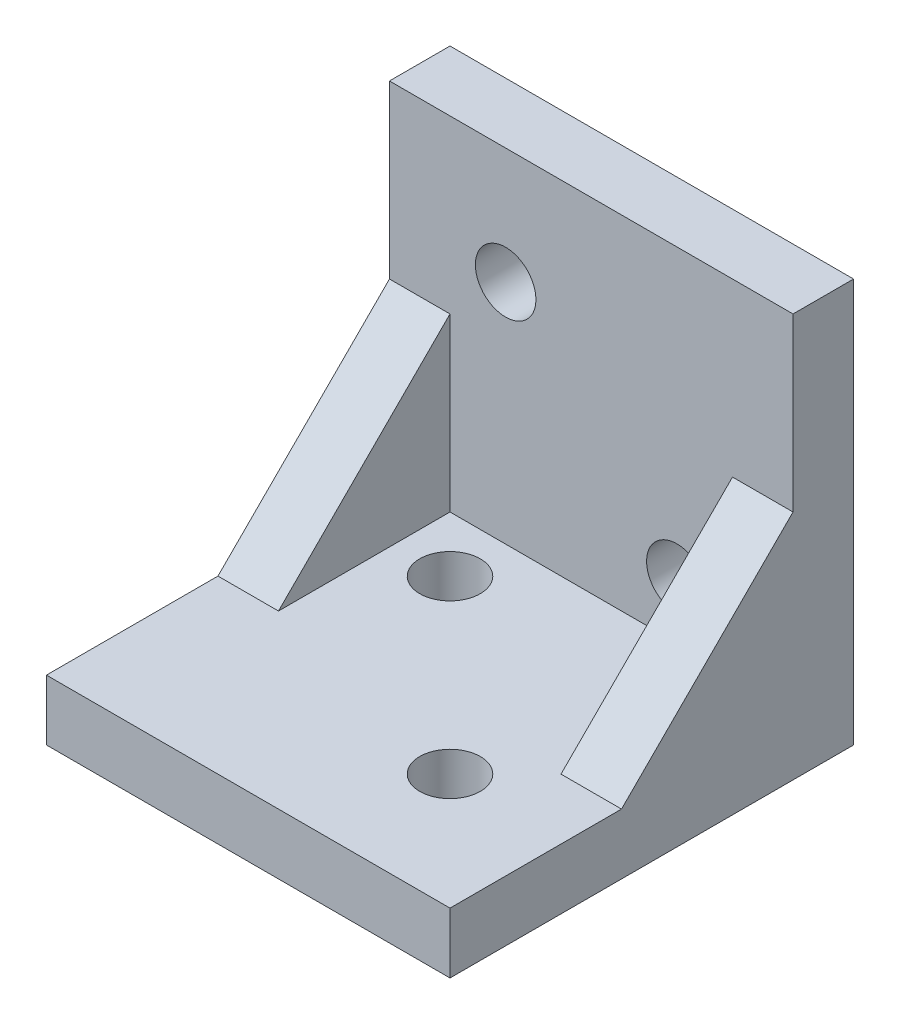
SolidWorks part; units mm, degrees
ref_plane "Front Plane" through (0, 0, 0) normal (0, 0, 1) x (1, 0, 0)
ref_plane "Top Plane" through (0, 0, 0) normal (0, 1, 0) x (1, 0, 0)
ref_plane "Right Plane" through (0, 0, 0) normal (1, 0, 0) x (0, 0, -1)
sketch "Sketch1" plane through (0, 0, 0) normal (0, 1, 0) x (1, 0, 0)
  line L0 (0, 0) -> (-10, 10) construction
  line L1 (-10, -10) -> (10, -10)
  line L2 (-10, -10) -> (-10, 10)
  line L3 (-10, 10) -> (10, 10)
  line L4 (10, -10) -> (10, 10)
  line L5 (-10, -10) -> (10, 10) construction
  line L7 (0, 0) -> (10, -10) construction
  circle A0 centre (-4.2426, 4.2426) radius 1.5
  circle A2 centre (4.2426, -4.2426) radius 1.5
  point P0 (0, 0)
  dimension "D3" = 3
  dimension "D4" = 3
  dimension "D1" = 20
  dimension "D2" = 20
  dimension "D5" = 6
extrude "Boss-Extrude1" add sketch "Sketch1" along normal blind 3
sketch "Sketch2" plane through (0, 3, 0) normal (0, 1, 0) x (1, 0, 0)
  line L0 (10, -10) -> (10, 10) construction
  line L1 (-10, 10) -> (10, 10)
  line L2 (-10, 10) -> (-10, 7)
  line L3 (-10, 7) -> (10, 7)
  line L4 (10, 10) -> (10, 7)
  dimension "D1" = 3
extrude "Boss-Extrude2" add sketch "Sketch2" along normal blind 17
sketch "Sketch3" plane through (0, 0, -10) normal (0, 0, -1) x (-1, 0, 0)
  line L1 (10, 20) -> (-10, 0) construction
  line L2 (11, 0) -> (-11, 0) construction
  line L3 (-10, 20) -> (10, 0) construction
  line L4 (-10, 20) -> (-10, 0) construction
  line L6 (-10, 20) -> (10, 20) construction
  line L7 (10, 20) -> (10, 0) construction
  circle A0 centre (-4.2426, 5.7574) radius 1.5
  circle A1 centre (4.2426, 14.2426) radius 1.5
  point P13 (4.8387, 14.9623)
  point P15 (-4.8593, 6.6849)
  point P20 (-4.9118, 6.4265)
  point P21 (0, 0)
  point P22 (0, 0)
  dimension "D2" = 3
  dimension "D3" = 3
  dimension "D1" = 6
extrude "Cut-Extrude1" cut sketch "Sketch3" against normal blind 30
sketch "Sketch4" plane through (-10, 0, 0) normal (-1, 0, 0) x (0, 0, 1)
  line L0 (-7, 11.5) -> (1.5, 3)
  line L1 (-7, 20) -> (-7, 3) construction
  line L2 (-7, 3) -> (10, 3) construction
  line L3 (1.5, 3) -> (-7, 3)
  line L4 (-7, 3) -> (-7, 11.5)
extrude "Boss-Extrude3" add sketch "Sketch4" against normal blind 3
extrude "Boss-Extrude4" add sketch "Sketch4<2>" along normal blind 3 from surface starting at face at (10, 7.6667, -2.3333)
sketch "Sketch4<2>" plane through (-10, 0, 0) normal (-1, 0, 0) x (0, 0, 1) same geometry as "Sketch4"
